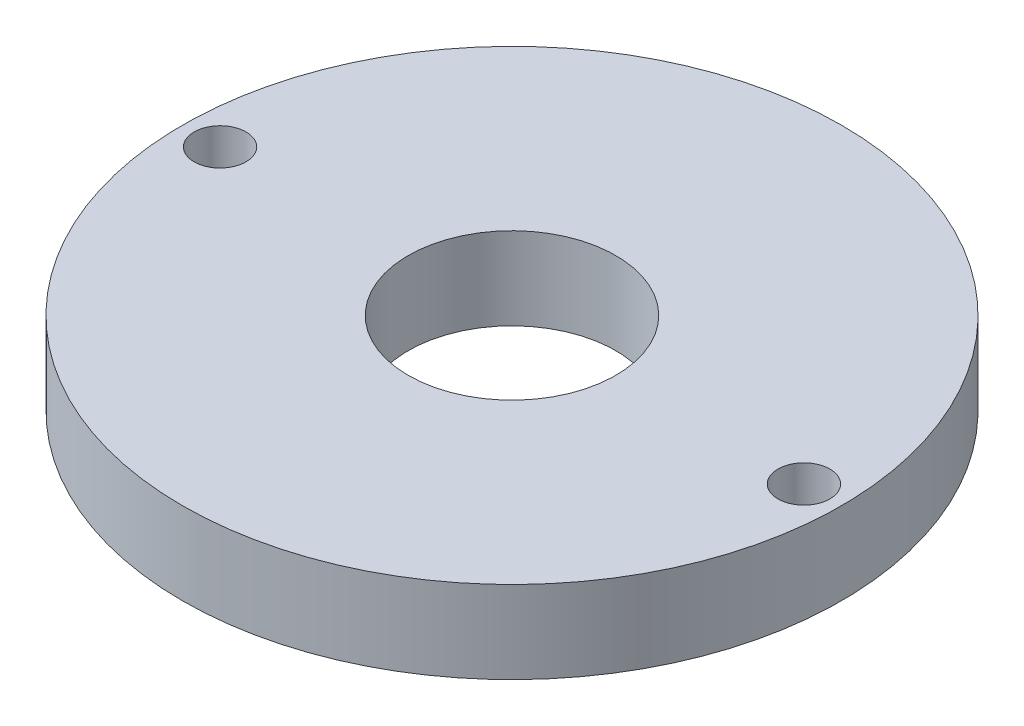
SolidWorks part; units mm, degrees
ref_plane "Front Plane" through (0, 0, 0) normal (0, 0, 1) x (1, 0, 0)
ref_plane "Top Plane" through (0, 0, 0) normal (0, 1, 0) x (1, 0, 0)
ref_plane "Right Plane" through (0, 0, 0) normal (1, 0, 0) x (0, 0, -1)
sketch "Sketch1" plane through (0, 0, 0) normal (0, 1, 0) x (1, 0, 0)
  circle A0 centre (0, 0) radius 50.8
  circle A1 centre (0, 0) radius 16
extrude "Boss-Extrude1" add sketch "Sketch1" along normal blind 12.7
sketch "Sketch2" plane through (0, 12.7, 0) normal (0, 1, 0) x (1, 0, 0)
  line L0 (0, 0) -> (45, 0)
  line L1 (0, 0) -> (-45, 0)
  circle A0 centre (-45, 0) radius 4
  circle A1 centre (45, 0) radius 4
  dimension "D1" = 45
  dimension "D2" = 45
extrude "Cut-Extrude1" cut sketch "Sketch2" against normal blind 12.7 contours A0 | A1 region at (45, 12.7, -3.8869) region at (-48.8869, 12.7, 0)
